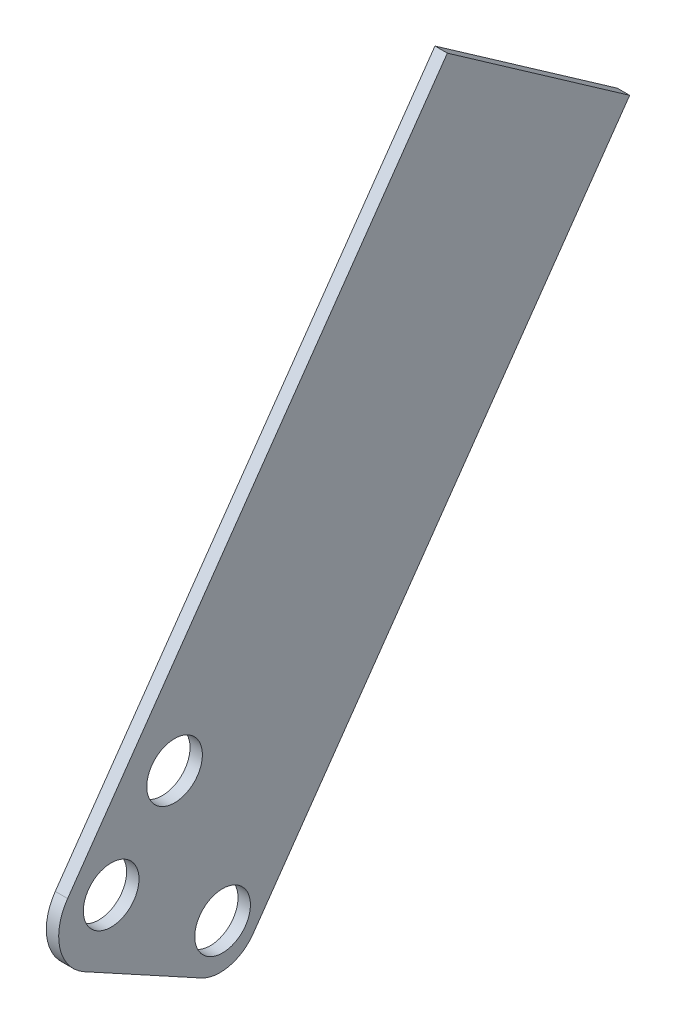
SolidWorks part; units mm, degrees
ref_plane "Front Plane" through (0, 0, 0) normal (0, 0, 1) x (1, 0, 0)
ref_plane "Top Plane" through (0, 0, 0) normal (0, 1, 0) x (1, 0, 0)
ref_plane "Right Plane" through (0, 0, 0) normal (1, 0, 0) x (0, 0, -1)
sketch "Sketch1" plane through (0, 0, 0) normal (1, 0, 0) x (0, 0, -1)
  line L0 (10.5948, 15.1309) -> (203.9638, 291.2905)
  line L1 (55, 0) -> (-55, 0) construction
  line L3 (110.3347, 356.8503) -> (-84.6362, 78.4029)
  line L4 (-76.0118, 41.546) -> (-16.2084, 8.8591)
  line L5 (110.3347, 356.8503) -> (203.9638, 291.2905)
  circle A0 centre (-62.2858, 68.8067) radius 14.2875
  circle A1 centre (-5.0681, 28.7424) radius 14.2875
  arc A2 (10.5948, 15.1309) -> (-16.2084, 8.8591) centre (-6.3105, 26.9681) cw
  arc A3 (-76.0118, 41.546) -> (-84.6362, 78.4029) centre (-63.8298, 63.834) cw
  circle A4 centre (-29.7169, 107.7927) radius 14.2875
  point P13 (0, 0)
  point P16 (-100.9135, 55.1566)
  dimension "D3" = 69.85
  dimension "D8" = 28.575
  dimension "D10" = 20.6375
  dimension "D11" = 25.4
  dimension "D12" = 82.804
  dimension "D13" = 28.575
  dimension "D1" = 355.6
  dimension "D2" = 55
  dimension "D4" = 40.9686
  dimension "D5" = 20.6375
  dimension "D6" = 368.3
  dimension "D7" = 28.7424
  dimension "D9" = 114.3
  dimension "D14" = 50.8
extrude "Boss-Extrude2" add sketch "Sketch1" along normal blind 3.175 and the other way blind 3.175
